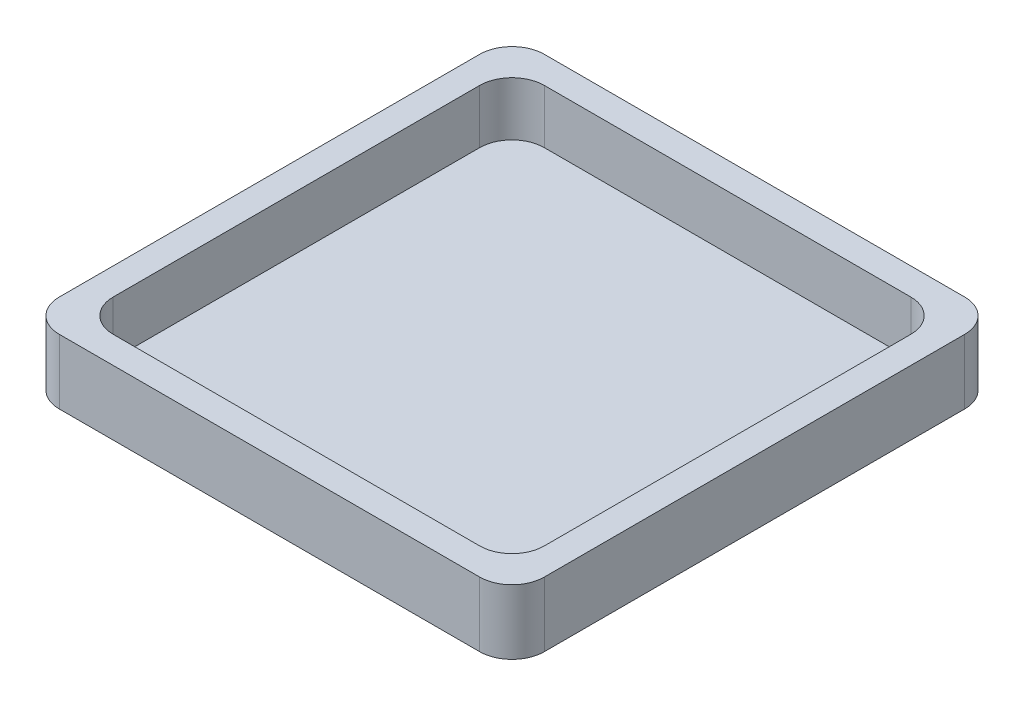
SolidWorks part; units mm, degrees
ref_plane "Front Plane" through (0, 0, 0) normal (0, 0, 1) x (1, 0, 0)
ref_plane "Top Plane" through (0, 0, 0) normal (0, 1, 0) x (1, 0, 0)
ref_plane "Right Plane" through (0, 0, 0) normal (1, 0, 0) x (0, 0, -1)
sketch "Sketch1" plane through (0, 0, 0) normal (0, 1, 0) x (1, 0, 0)
  line L1 (-20, -20) -> (20, -20)
  line L2 (-20, -20) -> (-20, 20)
  line L3 (-20, 20) -> (20, 20)
  line L4 (20, -20) -> (20, 20)
  line L5 (-20, -20) -> (20, 20) construction
  line L6 (-20, 20) -> (20, -20) construction
  line L7 (-22.5, -22.5) -> (22.5, -22.5)
  line L8 (-22.5, -22.5) -> (-22.5, 22.5)
  line L9 (-22.5, 22.5) -> (22.5, 22.5)
  line L10 (22.5, -22.5) -> (22.5, 22.5)
  line L11 (-22.5, -22.5) -> (22.5, 22.5) construction
  line L12 (-22.5, 22.5) -> (22.5, -22.5) construction
  point P0 (0, 0)
  point P6 (0, 0)
  dimension "D1" = 40
  dimension "D2" = 40
  dimension "D3" = 45
  dimension "D4" = 45
extrude "Boss-Extrude1" add sketch "Sketch1" along normal blind 1 contours L2 L1 L4 L3
extrude "Boss-Extrude2" add sketch "Sketch1<3>" along normal blind 6
sketch "Sketch1<3>" plane through (0, 0, 0) normal (0, 1, 0) x (1, 0, 0) same geometry as "Sketch1"
fillet "Fillet1" radius 3 8 edges at (22.5, 3, 22.5) (-20, 3.5, 20) (20, 3.5, 20) (20, 3.5, -20) (-20, 3.5, -20) (-22.5, 3, 22.5) (-22.5, 3, -22.5) (22.5, 3, -22.5)
